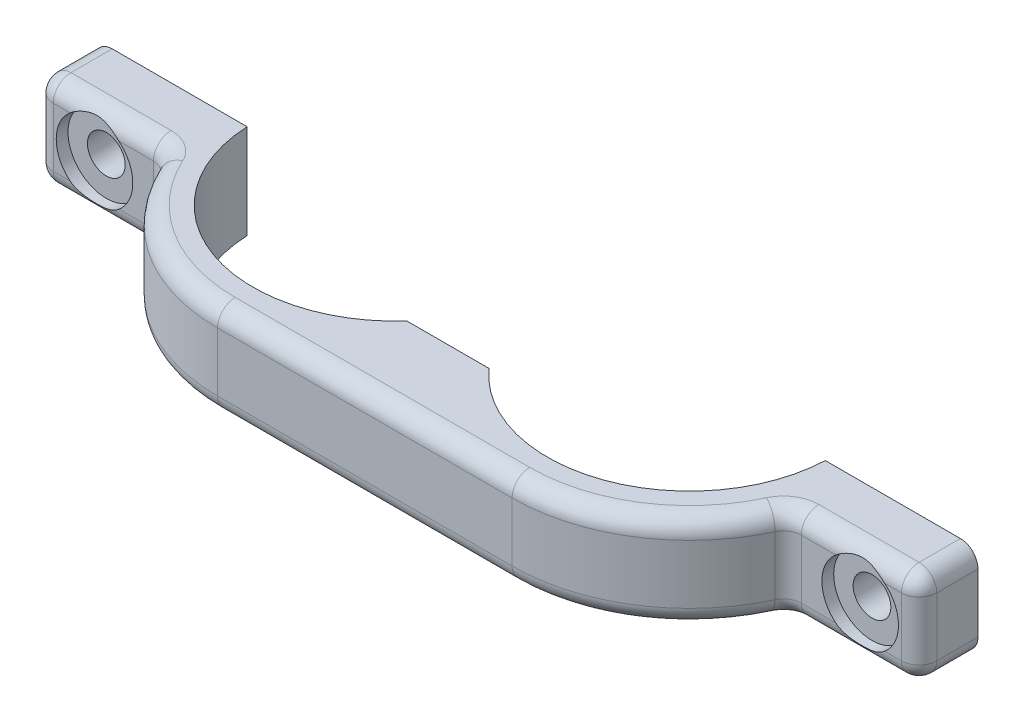
SolidWorks part; units mm, degrees
ref_plane "Plan de face" through (0, 0, 0) normal (0, 0, 1) x (1, 0, 0)
ref_plane "Plan de dessus" through (0, 0, 0) normal (0, 1, 0) x (1, 0, 0)
ref_plane "Plan de droite" through (0, 0, 0) normal (1, 0, 0) x (0, 0, -1)
sketch "Esquisse1" plane through (0, 0, 0) normal (0, 1, 0) x (1, 0, 0)
  line L6 (-12.5, 0) -> (12.5, 0) construction
  line L7 (-37.5, -0.5) -> (-24.5396, -0.5)
  line L8 (24.5396, -0.5) -> (37.5, -0.5)
  line L11 (12.5, -15.05) -> (-12.5, -15.05)
  line L13 (-37.5, -5.5) -> (-37.5, -0.5)
  line L14 (-3.4888, -8) -> (3.4888, -8)
  line L15 (-37.5, -5.5) -> (-26.509, -5.5)
  line L16 (0, -4.4) -> (0, 4.4) construction
  line L17 (37.5, -5.5) -> (26.509, -5.5)
  line L18 (37.5, -5.5) -> (37.5, -0.5)
  circle A0 centre (-12.5, 0) radius 12.05 construction
  circle A1 centre (12.5, 0) radius 12.05 construction
  arc A2 (-24.5396, -0.5) -> (-3.4888, -8) centre (-12.5, 0) ccw
  arc A3 (24.5396, -0.5) -> (3.4888, -8) centre (12.5, 0) cw
  arc A4 (-26.509, -5.5) -> (-12.5, -15.05) centre (-12.5, 0) ccw
  arc A5 (26.509, -5.5) -> (12.5, -15.05) centre (12.5, 0) cw
  point P23 (0, 0)
  dimension "D1" = 24.1
  dimension "D4" = 3
  dimension "D7" = 75
  dimension "D2" = 25
  dimension "D3" = 1
  dimension "D5" = 8
  dimension "D6" = 5
extrude "Boss.-Extru.1" add sketch "Esquisse1" along normal blind 8
sketch "Esquisse2" plane through (0, 0, 0.5) normal (0, 0, -1) x (-1, 0, 0)
  line L0 (3.4888, 8) -> (3.4888, 0) construction
  line L1 (0, 4.4) -> (0, -4.4) construction
  circle A0 centre (32.5, 4) radius 1.6
  circle A2 centre (-32.5, 4) radius 1.6
  point P4 (3.4888, 4)
  dimension "D1" = 3.2
  dimension "D2" = 65
extrude "Enlèv. mat.-Extru.1" cut sketch "Esquisse2" against normal through all
sketch "Esquisse3" plane through (0, 0, 0.5) normal (0, 0, -1) x (-1, 0, 0)
  circle A0 centre (32.5, 4) radius 3.25
  circle A1 centre (-32.5, 4) radius 3.25
  circle A2 centre (32.5, 4) radius 1.6 construction
  circle A3 centre (-32.5, 4) radius 1.6 construction
  dimension "D1" = 6.5
extrude "Enlèv. mat.-Extru.2" cut sketch "Esquisse3" against normal through all from offset 4 offset against normal yes
fillet "Congé1" radius 1.5 18 edges at (-37.5, 8, 3) (-37.5, 0, 3) (0, 8, 15.05) (0, 0, 15.05) (-20.9772, 8, 12.4354) (20.9772, 8, 12.4354) (-20.9772, 0, 12.4354) (20.9772, 0, 12.4354) (-32.0045, 8, 5.5) (32.0045, 8, 5.5) (-32.0045, 0, 5.5) (32.0045, 0, 5.5) (37.5, 0, 3) (37.5, 8, 3) (-26.509, 4, 5.5) (26.509, 4, 5.5) (37.5, 4, 5.5) (-37.5, 4, 5.5)
